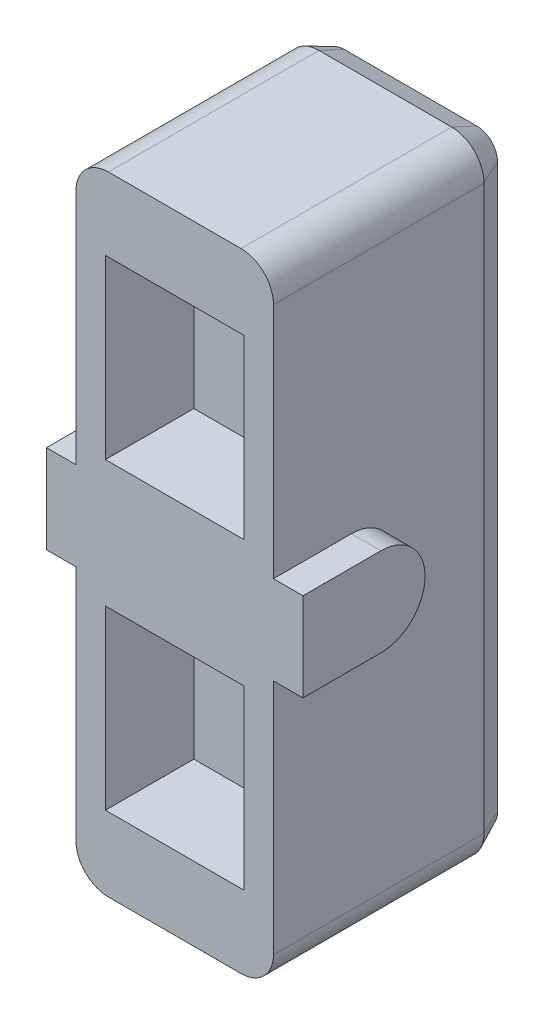
SolidWorks part; units mm, degrees
ref_plane "Plan de face" through (0, 0, 0) normal (0, 0, 1) x (1, 0, 0)
ref_plane "Plan de dessus" through (0, 0, 0) normal (0, 1, 0) x (1, 0, 0)
ref_plane "Plan de droite" through (0, 0, 0) normal (1, 0, 0) x (0, 0, -1)
sketch "Esquisse2" plane through (0, 0, 0) normal (0, 0, 1) x (1, 0, 0)
  line L1 (1.1, 0) -> (5.6, 0)
  line L2 (0, 1.1) -> (0, 20.2)
  line L3 (1.1, 21.3) -> (5.6, 21.3)
  line L4 (6.7, 1.1) -> (6.7, 20.2)
  arc A0 (5.6, 21.3) -> (6.7, 20.2) centre (5.6, 20.2) cw
  arc A1 (5.6, 0) -> (6.7, 1.1) centre (5.6, 1.1) ccw
  arc A2 (1.1, 0) -> (0, 1.1) centre (1.1, 1.1) cw
  arc A3 (0, 20.2) -> (1.1, 21.3) centre (1.1, 20.2) cw
  point P7 (6.7, 21.3)
  point P12 (0, 0)
  point P15 (0, 21.3)
  dimension "D3" = 1.1
  dimension "D1" = 6.7
  dimension "D2" = 21.3
extrude "Boss.-Extru.1" add sketch "Esquisse2" along normal blind 8
sketch "Esquisse3" plane through (0, 0, 8) normal (0, 0, 1) x (1, 0, 0)
  line L0 (0, 20.2) -> (0, 1.1) construction
  line L1 (1, 18.8) -> (5.7, 18.8)
  line L2 (1, 18.8) -> (1, 12.8)
  line L3 (1, 12.8) -> (5.7, 12.8)
  line L4 (5.7, 18.8) -> (5.7, 12.8)
  line L5 (6.7, 1.1) -> (6.7, 20.2) construction
  line L6 (5.6, 21.3) -> (1.1, 21.3) construction
  line L8 (1.1, 0) -> (5.6, 0) construction
  line L9 (1, 8.5) -> (5.7, 8.5)
  line L10 (1, 8.5) -> (1, 2.5)
  line L11 (1, 2.5) -> (5.7, 2.5)
  line L12 (5.7, 8.5) -> (5.7, 2.5)
  line L13 (-7.1761, 15.8) -> (15.2275, 15.8) construction
  dimension "D2" = 6
  dimension "D3" = 1
  dimension "D4" = 1
  dimension "D5" = 2.5
  dimension "D6" = 6
  dimension "D8" = 1
  dimension "D9" = 2.5
  dimension "D10" = 5.5
  dimension "D11" = 1
chamfer "Chanfrein1" distance 0.4 angle 65 8 edges at (3.35, 0, 0) (6.3778, 0.3222, 0) (0.3222, 0.3222, 0) (6.7, 10.65, 0) (0, 10.65, 0) (6.3778, 20.9778, 0) (0.3222, 20.9778, 0) (3.35, 21.3, 0) first distance on face at (3.35, 10.65, 0)
sketch "Esquisse5" plane through (0, 0, 0) normal (0, 0, 1) x (1, 0, 0)
  line L1 (1.54, 5.9) -> (5.1595, 5.9)
  line L2 (5.1595, 5.9) -> (3.3498, 1.9)
  line L3 (3.3498, 1.9) -> (1.54, 5.9)
  line L4 (3.3498, 3.3556) -> (2.47, 5.3)
  line L5 (2.47, 5.3) -> (4.2295, 5.3)
  line L6 (4.2295, 5.3) -> (3.3498, 3.3556)
  line L7 (5.6, 0.4) -> (1.1, 0.4) construction
  line L8 (1.54, 15.4) -> (5.16, 15.4)
  line L9 (5.16, 15.4) -> (3.35, 19.4)
  line L10 (3.35, 19.4) -> (1.54, 15.4)
  line L11 (2.4701, 16) -> (4.2299, 16)
  line L12 (4.2299, 16) -> (3.35, 17.9446)
  line L13 (3.35, 17.9446) -> (2.4701, 16)
  line L14 (1.1, 20.9) -> (5.6, 20.9) construction
  line L15 (0.4, 1.1) -> (0.4, 20.2) construction
  line L16 (6.3, 20.2) -> (6.3, 1.1) construction
  dimension "D1" = 0.6
  dimension "D2" = 0.6
  dimension "D3" = 0.6
  dimension "D4" = 1.8098
  dimension "D5" = 1.8097
  dimension "D6" = 4
  dimension "D7" = 1.5
  dimension "D8" = 0.6
  dimension "D9" = 0.6
  dimension "D10" = 0.6
  dimension "D11" = 4
  dimension "D12" = 1.81
  dimension "D13" = 1.81
  dimension "D14" = 1.5
  dimension "D15" = 1.14
  dimension "D16" = 1.1405
  dimension "D17" = 1.14
extrude "Enlèv. mat.-Extru.3" cut sketch "Esquisse5" along normal blind 0.2
extrude "Boss.-Extru.2" add sketch "Esquisse5<4>" against normal blind 0.2
sketch "Esquisse5<4>" plane through (0, 0, 0) normal (0, 0, 1) x (1, 0, 0) same geometry as "Esquisse5"
extrude "Enlèv. mat.-Extru.4" cut sketch "Esquisse3" against normal blind 3
sketch "Esquisse6" plane through (0, 0, 0) normal (-1, 0, 0) x (0, 0, 1)
  line L0 (-8.8899, 10.65) -> (18.0179, 10.65) construction
  line L1 (8, 20.2) -> (0.8578, 20.2) construction
  line L2 (8, 1.1) -> (0.8578, 1.1) construction
  line L3 (0.8578, 20.2) -> (0.8578, 1.1) construction
  line L5 (5.3578, 12.15) -> (8, 12.15)
  line L6 (8, 1.1) -> (8, 20.2) construction
  line L7 (8, 12.15) -> (8, 9.15)
  line L8 (8, 9.15) -> (5.3578, 9.15)
  arc A0 (5.3578, 9.15) -> (5.3578, 12.15) centre (5.3578, 10.65) cw
  dimension "D4" = 1.5
  dimension "D1" = 9.55
  dimension "D2" = 9.55
  dimension "D3" = 0
  dimension "D5" = 4.5
extrude "Boss.-Extru.3" add sketch "Esquisse6" along normal blind 1 and the other way blind 7.7
